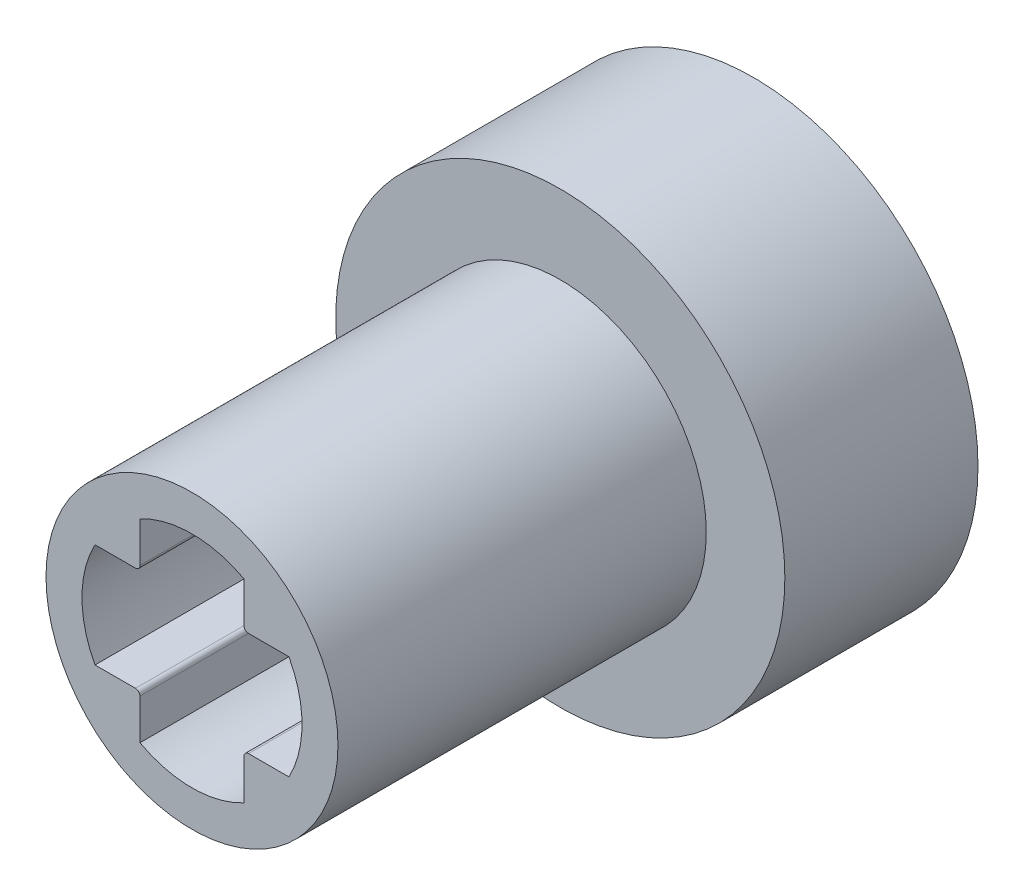
SolidWorks part; units mm, degrees
ref_plane "前视基准面" through (0, 0, 0) normal (0, 0, 1) x (1, 0, 0)
ref_plane "上视基准面" through (0, 0, 0) normal (0, 1, 0) x (1, 0, 0)
ref_plane "右视基准面" through (0, 0, 0) normal (1, 0, 0) x (0, 0, -1)
other "Configuration Table"
sketch "草图1" plane through (0, 0, 0) normal (0, 0, 1) x (1, 0, 0)
  circle A0 centre (0, 0) radius 1.15
  circle A1 centre (0, 0) radius 5
  dimension "D1" = 2.3
  dimension "D2" = 10
extrude "凸台-拉伸1" add sketch "草图1" along normal blind 12.5
sketch "草图2" plane through (0, 0, 12.5) normal (0, 0, 1) x (1, 0, 0)
  line L0 (1.1587, 1.1587) -> (2.1587, 1.1587)
  line L2 (1.1587, -2.1587) -> (1.1587, -1.1587)
  line L4 (-1.1587, -2.1587) -> (-1.1587, -1.1587)
  line L5 (-1.1587, 1.1587) -> (-1.1587, 2.1587)
  line L6 (1.1587, 1.1587) -> (1.1587, 2.1587)
  line L7 (-2.1587, -1.1587) -> (-1.1587, -1.1587)
  line L9 (-2.1587, 1.1587) -> (-1.1587, 1.1587)
  line L15 (1.1587, -1.1587) -> (2.1587, -1.1587)
  circle A9 centre (0, 0) radius 3.25
  circle A10 centre (0, 0) radius 2.45
  circle M5 centre (0, 0) radius 5
  circle M6 centre (0, 0) radius 1.15
  dimension "D3" = 6.5
  dimension "D1" = 4.9
  dimension "D4" = 1
extrude "切除-拉伸5" cut sketch "草图2" against normal blind 8.2 contours A9 M5 region at (-4.8586, 0, 12.5)
extrude "切除-拉伸6" cut sketch "草图2<7>" against normal blind 8 contours L6 A10 L5 L9 L7 L4 L2 L15 L0 M6 region at (1.6587, 1.0894, 12.5)
sketch "草图2<7>" plane through (0, 0, 12.5) normal (0, 0, 1) x (1, 0, 0) same geometry as "草图2"
fillet "圆角1" radius 0.1 4 edges at (1.1587, -1.1587, 8.5) (1.1587, 1.1587, 8.5) (-1.1587, 1.1587, 8.5) (-1.1587, -1.1587, 8.5)
